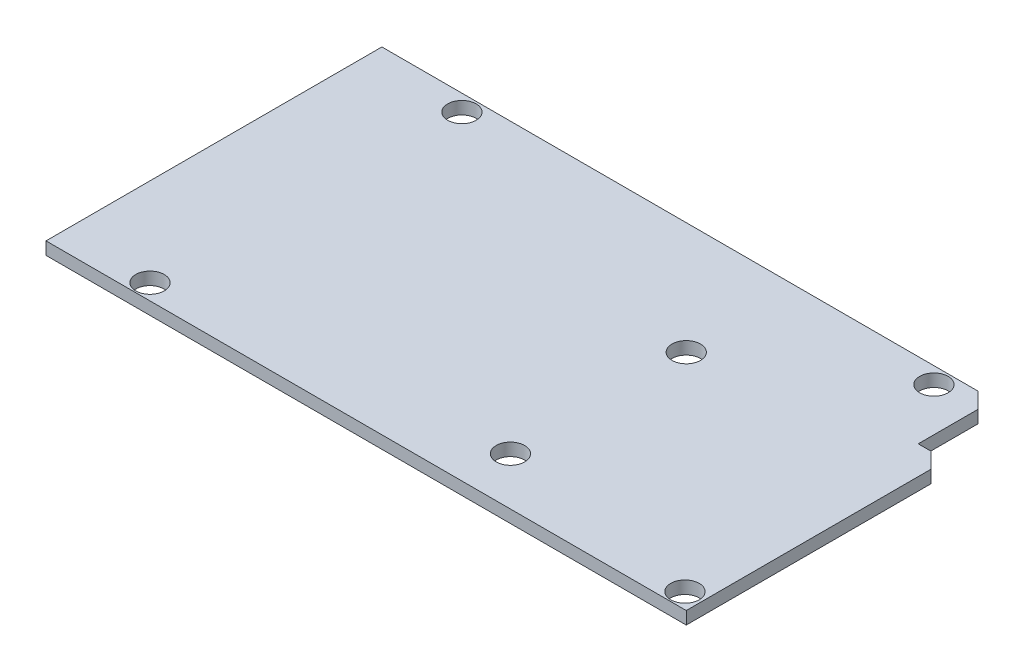
SolidWorks part; units mm, degrees
ref_plane "Front Plane" through (0, 0, 0) normal (0, 0, 1) x (1, 0, 0)
ref_plane "Top Plane" through (0, 0, 0) normal (0, 1, 0) x (1, 0, 0)
ref_plane "Right Plane" through (0, 0, 0) normal (1, 0, 0) x (0, 0, -1)
sketch "Sketch1" plane through (0, 0, 0) normal (0, 1, 0) x (1, 0, 0)
  line L0 (-35.6943, 0) -> (-35.6943, 53.3)
  line L1 (-35.6943, 0) -> (65.9057, 0)
  line L2 (-35.6943, 53.3) -> (58.9018, 53.3)
  line L3 (61.4018, 50.8) -> (61.4018, 41.3163)
  line L4 (61.4018, 41.3163) -> (63.4057, 41.3163)
  line L5 (65.9057, 38.8163) -> (65.9057, 0)
  line L6 (58.9018, 53.3) -> (61.4018, 50.8)
  line L7 (63.4057, 41.3163) -> (65.9057, 38.8163)
  point P5 (61.4018, 53.3)
  point P7 (65.9057, 41.3163)
  dimension "D1" = 53.3
  dimension "D2" = 101.6
extrude "Boss-Extrude1" add sketch "Sketch1" along normal blind 2
sketch "Sketch2" plane through (0, 2, 0) normal (0, 1, 0) x (1, 0, 0)
  line L0 (-35.6943, 53.3) -> (-21.6943, 53.3)
  line L1 (58.9018, 53.3) -> (-35.6943, 53.3) construction
  line L2 (65.9057, 0) -> (63.2013, 0) construction
  line L3 (-35.6943, 0) -> (65.9057, 0) construction
  line L4 (-21.6943, 0) -> (-21.6943, 2.5) construction
  line L5 (63.2013, 0) -> (63.2013, 2.5) construction
  line L6 (63.2013, 2.5) -> (63.2013, 7.6) construction
  line L7 (-21.6943, 53.3) -> (-20.3943, 53.3) construction
  line L8 (-20.3943, 53.3) -> (30.4057, 53.3) construction
  line L9 (30.4057, 35.5) -> (30.4057, 50.7) construction
  line L10 (63.2013, 7.6) -> (30.4057, 7.6) construction
  line L11 (30.4057, 7.6) -> (30.4057, 35.5) construction
  line L12 (30.4057, 50.7) -> (54.5057, 50.7) construction
  line L13 (30.4057, 50.7) -> (-20.3943, 50.7) construction
  circle A0 centre (-20.3943, 50.7) radius 2.261
  circle A1 centre (-21.6943, 2.5) radius 2.261
  circle A2 centre (63.2013, 2.5) radius 2.261
  circle A3 centre (30.4057, 7.6) radius 2.261
  circle A4 centre (30.4057, 35.5) radius 2.261
  circle A5 centre (54.5057, 50.7) radius 2.261
  dimension "D9" = 4.522
  dimension "D10" = 4.522
  dimension "D11" = 4.522
  dimension "D12" = 4.522
  dimension "D13" = 4.522
  dimension "D14" = 4.522
  dimension "D1" = 14
  dimension "D2" = 2.5
  dimension "D3" = 5.1
  dimension "D4" = 1.3
  dimension "D5" = 50.8
  dimension "D6" = 27.9
  dimension "D7" = 15.2
  dimension "D8" = 24.1
extrude "Cut-Extrude1" cut sketch "Sketch2" against normal blind 4 contours A0
extrude "Cut-Extrude2" cut sketch "Sketch2<3>" against normal blind 4 contours A1 | A3 | A4 | A5 | A2
sketch "Sketch2<3>" plane through (0, 2, 0) normal (0, 1, 0) x (1, 0, 0) same geometry as "Sketch2"
